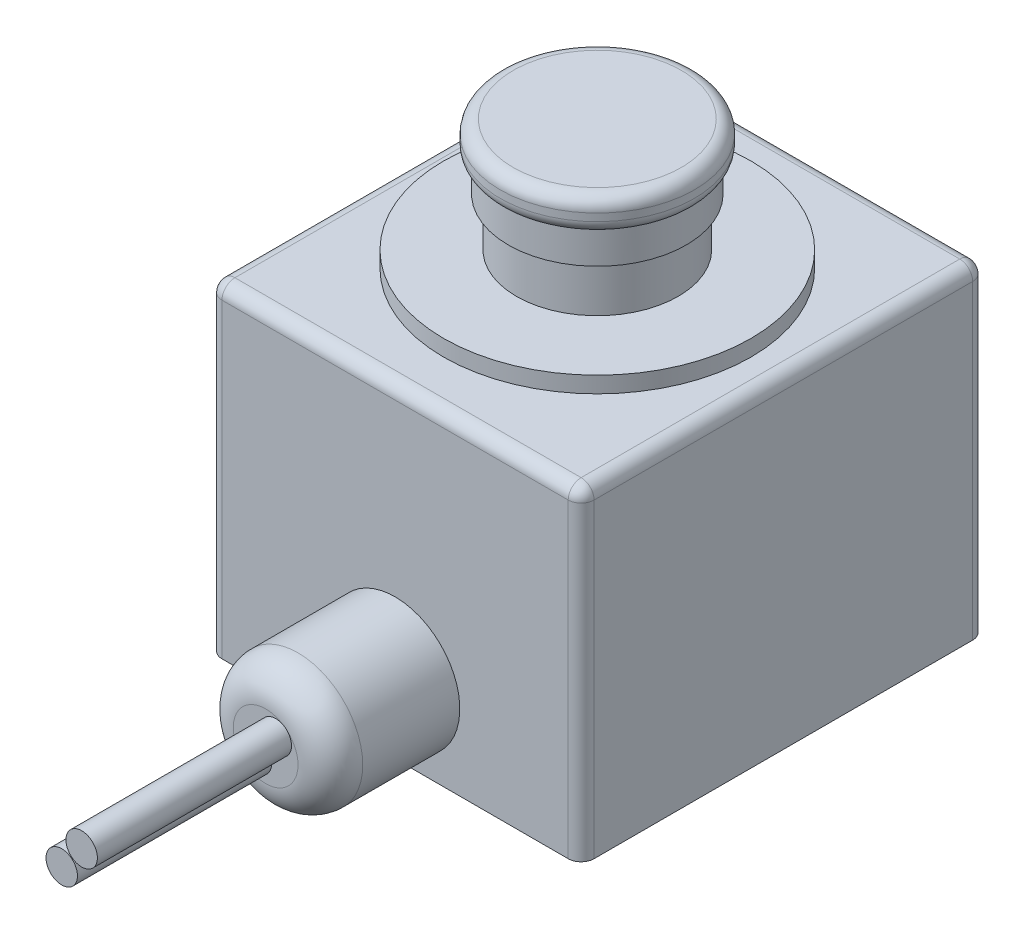
SolidWorks part; units mm, degrees
ref_plane "Front Plane" through (0, 0, 0) normal (0, 0, 1) x (1, 0, 0)
ref_plane "Top Plane" through (0, 0, 0) normal (0, 1, 0) x (1, 0, 0)
ref_plane "Right Plane" through (0, 0, 0) normal (1, 0, 0) x (0, 0, -1)
sketch "Sketch1" plane through (0, 0, 0) normal (0, 1, 0) x (1, 0, 0)
  line L0 (0, 79.375) -> (73.025, 0) construction
  line L1 (0, 0) -> (73.025, 0)
  line L2 (0, 0) -> (0, 79.375)
  line L3 (0, 79.375) -> (73.025, 79.375)
  line L4 (73.025, 0) -> (73.025, 79.375)
  line L5 (73.025, 79.375) -> (0, 0) construction
  dimension "D1" = 73.025
  dimension "D2" = 79.375
extrude "Boss-Extrude1" add sketch "Sketch1" along normal blind 63.5 contours L3 L4 L1 L2
sketch "Sketch2" plane through (0, 63.5, 0) normal (0, 1, 0) x (1, 0, 0)
  line L0 (0, 79.375) -> (73.025, 0) construction
  line L1 (0, 0) -> (73.025, 79.375) construction
  circle A0 centre (36.5125, 39.6875) radius 15.875
  dimension "D1" = 31.75
extrude "Boss-Extrude2" add sketch "Sketch2" along normal blind 12.7
sketch "Sketch3" plane through (0, 63.5, 0) normal (0, 1, 0) x (1, 0, 0)
  line L0 (0, 39.6875) -> (73.025, 39.6875) construction
  line L1 (0, 0) -> (0, 79.375) construction
  line L2 (73.025, 0) -> (73.025, 79.375) construction
  line L3 (36.5125, 79.375) -> (36.5125, 0) construction
  line L4 (0, 79.375) -> (73.025, 79.375) construction
  line L5 (0, 0) -> (73.025, 0) construction
  circle A0 centre (36.5125, 39.6875) radius 30.1625
  dimension "D1" = 60.325
extrude "Boss-Extrude3" add sketch "Sketch3" along normal blind 3.175
sketch "Sketch4" plane through (0, 76.2, 0) normal (0, 1, 0) x (1, 0, 0)
  line L0 (73.025, 0) -> (0, 79.375) construction
  line L1 (0, 0) -> (73.025, 79.375) construction
  circle A0 centre (36.5125, 39.6875) radius 17.4625
  dimension "D1" = 34.925
extrude "Boss-Extrude4" add sketch "Sketch4" along normal blind 6.35
sketch "Sketch5" plane through (0, 82.55, 0) normal (0, 1, 0) x (1, 0, 0)
  line L0 (73.025, 0) -> (0, 79.375) construction
  line L1 (0, 79.375) -> (0, 0) construction
  line L2 (0, 0) -> (73.025, 79.375) construction
  circle A0 centre (36.5125, 39.6875) radius 19.05
  dimension "D1" = 38.1
extrude "Boss-Extrude5" add sketch "Sketch5" along normal blind 6.35 contours A0
fillet "Fillet1" radius 2.54 2 edges at (36.5125, 82.55, -20.6375) (36.5125, 88.9, -20.6375)
fillet "Fillet2" radius 2.54 4 edges at (73.025, 31.75, -79.375) (73.025, 31.75, 0) (0, 31.75, 0) (0, 31.75, -79.375)
fillet "Fillet5" radius 2.54 8 edges at (72.2811, 63.5, -78.6311) (0.7439, 63.5, -78.6311) (0.7439, 63.5, -0.7439) (72.2811, 63.5, -0.7439) (73.025, 63.5, -39.6875) (36.5125, 63.5, 0) (36.5125, 63.5, -79.375) (0, 63.5, -39.6875)
sketch "Sketch7" plane through (0, 0, 0) normal (0, 0, 1) x (1, 0, 0)
  line L0 (70.485, 0) -> (2.54, 60.96) construction
  line L1 (2.54, 60.96) -> (70.485, 60.96) construction
  line L2 (70.485, 60.96) -> (2.54, 0) construction
  line L3 (2.54, 0) -> (36.5125, 30.48) construction
  line L4 (36.5125, 30.48) -> (36.5125, 60.96) construction
  line L5 (36.5125, 60.96) -> (36.5125, 0) construction
  circle A0 centre (36.5125, 14.8342) radius 12.7
  dimension "D1" = 25.4
extrude "Boss-Extrude7" add sketch "Sketch7" along normal blind 25.4
fillet "Fillet6" radius 6.35 1 edges at (49.2125, 14.8342, 25.4)
sketch "Sketch8" plane through (0, 0, 25.4) normal (0, 0, 1) x (1, 0, 0)
  circle A0 centre (38.5061, 17.4404) radius 3.0864
  circle A1 centre (34.5961, 12.4291) radius 3.0864
extrude "Boss-Extrude8" add sketch "Sketch8" along normal blind 38.1
